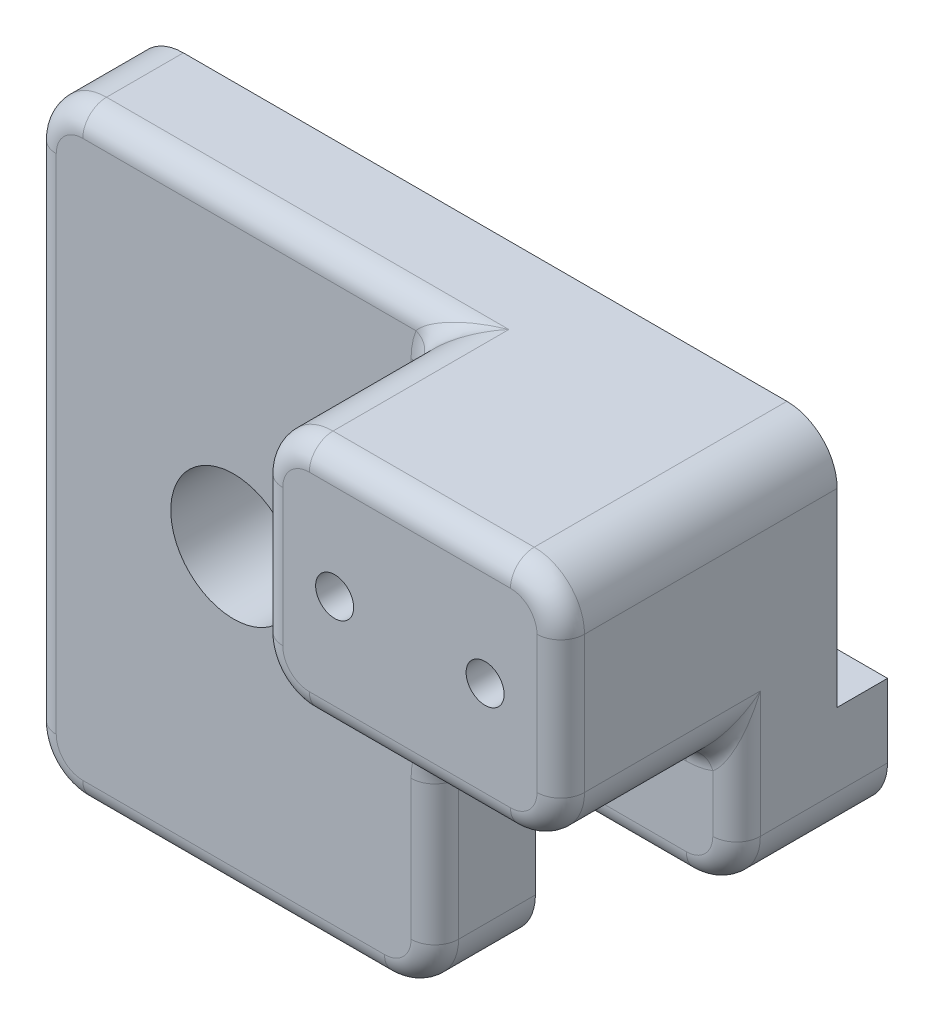
SolidWorks part; units mm, degrees
ref_plane "Front Plane" through (0, 0, 0) normal (0, 0, 1) x (1, 0, 0)
ref_plane "Top Plane" through (0, 0, 0) normal (0, 1, 0) x (1, 0, 0)
ref_plane "Right Plane" through (0, 0, 0) normal (1, 0, 0) x (0, 0, -1)
sketch "Sketch1" plane through (0, 0, 0) normal (0, 0, 1) x (1, 0, 0)
  line L1 (0, 0) -> (44.45, 0)
  line L2 (0, 0) -> (0, 38.1)
  line L3 (0, 38.1) -> (44.45, 38.1)
  line L4 (44.45, 0) -> (44.45, 38.1)
  line L5 (0, 0) -> (44.45, 38.1) construction
  line L6 (0, 38.1) -> (44.45, 0) construction
  point P4 (22.225, 19.05)
  dimension "D1" = 44.45
  dimension "D2" = 38.1
extrude "Boss-Extrude1" add sketch "Sketch1" along normal blind 6.35 contours L3 L4 L1 L2
sketch "Sketch2" plane through (0, 0, 6.35) normal (0, 0, 1) x (1, 0, 0)
  line L0 (0, 0) -> (44.45, 0) construction
  line L1 (0, 0) -> (0, 38.1) construction
  circle A0 centre (12.7, 19.05) radius 3.97
  dimension "D1" = 7.94
  dimension "D2" = 19.05
  dimension "D3" = 12.7
sketch "Sketch4" plane through (44.45, 0, 0) normal (1, 0, 0) x (0, 0, -1)
  line L0 (0, 0) -> (0, 38.1) construction
  line L1 (0, 22.95) -> (3.18, 22.95)
  line L2 (0, 22.95) -> (0, 15.15)
  line L3 (0, 15.15) -> (3.18, 15.15)
  line L4 (3.18, 22.95) -> (3.18, 15.15)
  line L5 (0, 22.95) -> (3.18, 15.15) construction
  line L6 (0, 15.15) -> (3.18, 22.95) construction
  line L7 (-6.35, 0) -> (0, 0) construction
  point P4 (1.59, 19.05)
  dimension "D1" = 7.8
  dimension "D2" = 19.05
  dimension "D3" = 3.18
extrude "Boss-Extrude2" add sketch "Sketch4" against normal up to surface (44.45 mm away) up to face at (0, 19.05, 3.175)
extrude "Cut-Extrude1" cut sketch "Sketch2" against normal through all contours A0
sketch "Sketch6" plane through (0, 0, 6.35) normal (0, 0, 1) x (1, 0, 0)
  line L0 (13.4422, 15.15) -> (44.45, 15.15) construction
  line L1 (0, 38.1) -> (44.45, 38.1) construction
  line L3 (44.45, 0) -> (44.45, 38.1) construction
  line L4 (25.4, 15.15) -> (44.45, 15.15)
  line L10 (25.4, 15.15) -> (25.4, 0)
  line L11 (0, 0) -> (44.45, 0) construction
  line L12 (25.4, 0) -> (44.45, 0)
  line L13 (44.45, 0) -> (44.45, 15.15)
  line L14 (30.175, 30.6) -> (39.675, 30.6) construction
  circle A6 centre (12.7, 19.05) radius 3.97 construction
  circle A7 centre (30.175, 30.6) radius 1.2
  circle A8 centre (39.675, 30.6) radius 1.2
  point P13 (0, 0)
  point P30 (34.925, 30.6)
  dimension "D2" = 9.525
  dimension "D3" = 2.4
  dimension "D4" = 12.7
  dimension "D5" = 9.5
  dimension "D1" = 7.5
extrude "Cut-Extrude3" cut sketch "Sketch6" against normal through all
sketch "Sketch8" plane through (0, 0, 6.35) normal (0, 0, 1) x (1, 0, 0)
  line L1 (44.45, 38.1) -> (25.4, 38.1)
  line L2 (44.45, 38.1) -> (44.45, 23.1)
  line L3 (44.45, 23.1) -> (25.4, 23.1)
  line L4 (25.4, 38.1) -> (25.4, 23.1)
  line L5 (44.45, 38.1) -> (25.4, 23.1) construction
  line L6 (44.45, 23.1) -> (25.4, 38.1) construction
  circle A0 centre (39.675, 30.6) radius 1.2 construction
  circle A1 centre (30.175, 30.6) radius 1.2 construction
  circle A2 centre (39.675, 30.6) radius 1.2
  circle A3 centre (30.175, 30.6) radius 1.2
  point P4 (34.925, 30.6)
  point P13 (0, 0)
  dimension "D1" = 7.5
  dimension "D2" = 19.05
extrude "Boss-Extrude4" add sketch "Sketch8" along normal blind 11.1
fillet "Fillet1" radius 3.175 9 edges at (0, 0, 3.175) (25.4, 0, 3.175) (44.45, 23.1, 11.9) (25.4, 23.1, 11.9) (25.4, 38.1, 11.9) (44.45, 38.1, 8.725) (0, 38.1, 3.175) (25.4, 15.15, 3.175) (44.45, 15.15, 1.585) tangent propagation no
fillet "Fillet5" radius 1.5 16 edges at (25.4, 30.6, 17.45) (26.3299, 37.1701, 17.45) (34.925, 38.1, 17.45) (43.5201, 37.1701, 17.45) (44.45, 30.6, 17.45) (43.5201, 24.0299, 17.45) (34.925, 23.1, 17.45) (25.4, 7.575, 6.35) (24.4701, 0.9299, 6.35) (12.7, 0, 6.35) (0.9299, 0.9299, 6.35) (15.875, 38.1, 6.35) (0.9299, 37.1701, 6.35) (26.3299, 24.0299, 17.45) (0, 19.05, 6.35) (26.3299, 14.2201, 6.35)
fillet "Fillet6" radius 1.5 7 edges at (27.0525, 37.7111, 5.8577) (25.5218, 35.7959, 6.35) (26.3299, 24.0299, 6.35) (25.4, 30.6, 6.35) (42.1459, 23.2218, 6.35) (34.925, 23.1, 6.35) (44.0611, 24.7525, 5.8577)
